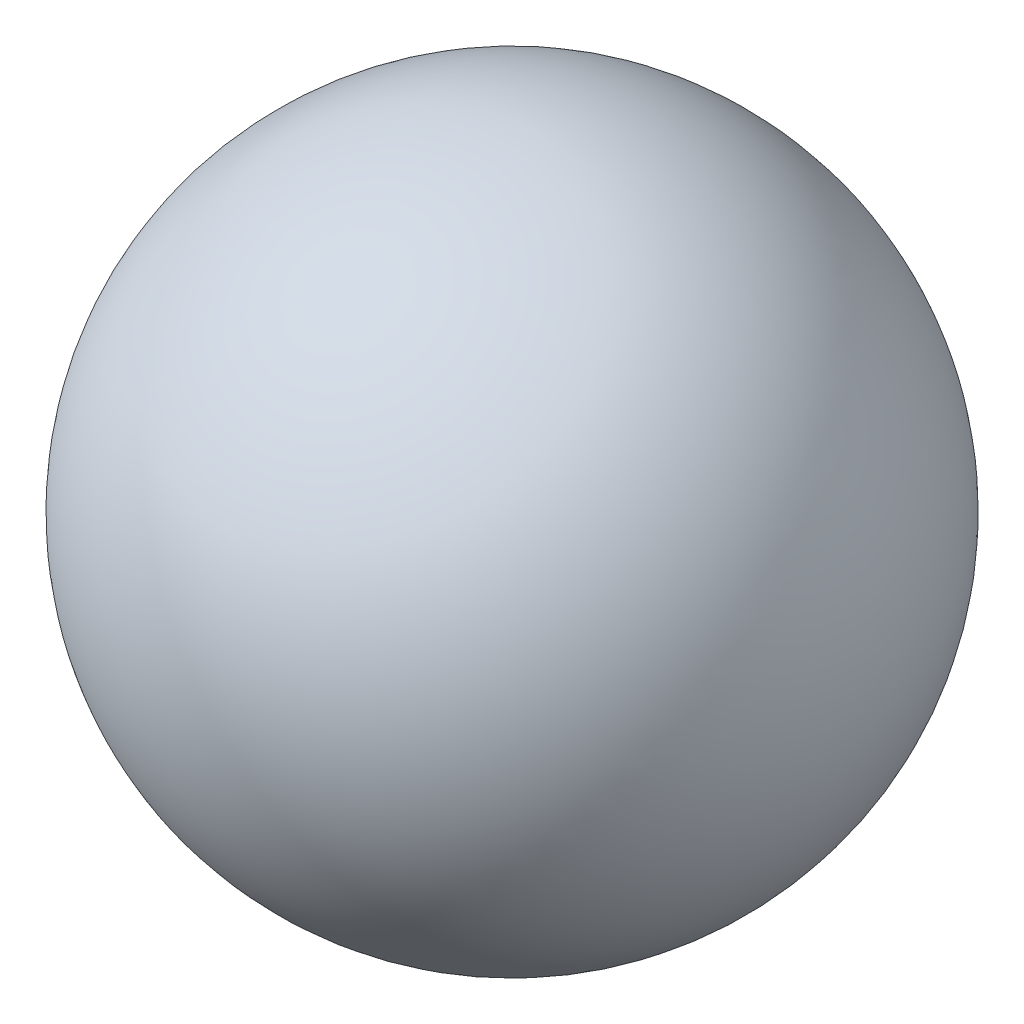
SolidWorks part; units mm, degrees
note: '?' marks a value the reader was unsure of.
ref_plane "Front Plane" through (0, 0, 0) normal (0, 0, 1) x (1, 0, 0)
ref_plane "Top Plane" through (0, 0, 0) normal (0, 1, 0) x (1, 0, 0)
ref_plane "Right Plane" through (0, 0, 0) normal (1, 0, 0) x (0, 0, -1)
sketch "Sketch2" plane through (0, 0, 0) normal (0, 1, 0) x (1, 0, 0)
  arc A1 (0, -20.32) -> (0, 20.32) centre (0, 0) cw
  dimension "D1" = 20.32
sketch "Sketch3" plane through (0, 0, 0) normal (0, 1, 0) x (1, 0, 0)
  line L0 (0, -1000) -> (0, 49000) construction
ref_axis "Axis1" through (0, 0, 1000) along (0, 0, -1)?
revolve "Revolve-Thin1" add sketch "Sketch2" angle 360 about L0
